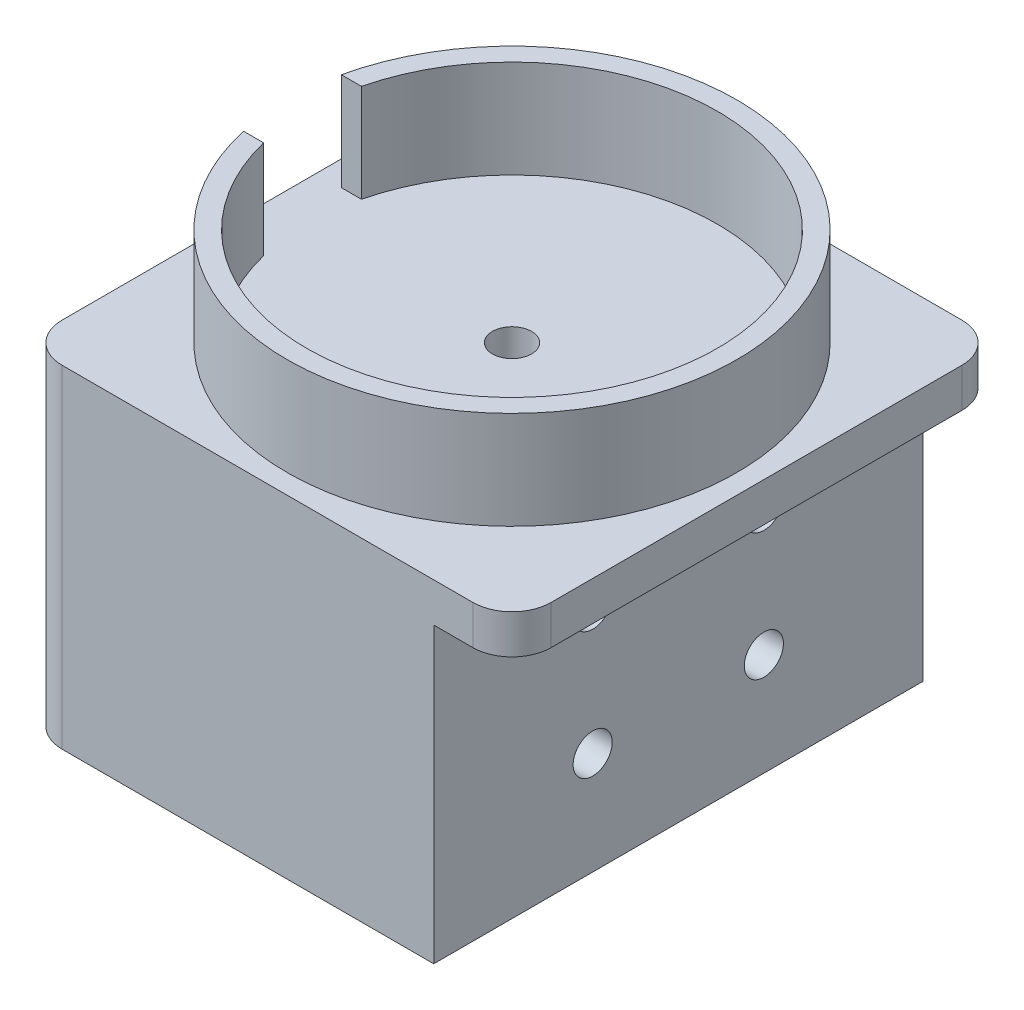
SolidWorks part; units mm, degrees
ref_plane "Front Plane" through (0, 0, 0) normal (0, 0, 1) x (1, 0, 0)
ref_plane "Top Plane" through (0, 0, 0) normal (0, 1, 0) x (1, 0, 0)
ref_plane "Right Plane" through (0, 0, 0) normal (1, 0, 0) x (0, 0, -1)
sketch "Sketch1" plane through (0, 0, 0) normal (0, 1, 0) x (1, 0, 0)
  line L0 (42, 50) -> (42, 0)
  line L1 (4, 0) -> (50, 0)
  line L2 (0, 4) -> (0, 46)
  line L3 (4, 50) -> (50, 50)
  line L4 (50, 0) -> (50, 50)
  arc A0 (4, 0) -> (0, 4) centre (4, 4) cw
  arc A1 (0, 46) -> (4, 50) centre (4, 46) cw
  point P7 (0, 0)
  point P10 (0, 50)
  dimension "D3" = 4
  dimension "D1" = 50
  dimension "D2" = 50
  dimension "D4" = 8
extrude "Boss-Extrude1" add sketch "Sketch1" along normal blind 30 contours A1 L2 A0 L1 L0 L3 region at (21.066, 0, -25)
sketch "Sketch3" plane through (0, 0, 0) normal (0, 0, 1) x (1, 0, 0)
  line L0 (42, 30) -> (42, 0) construction
  line L1 (34, 4) -> (0, 4)
  line L2 (34, 4) -> (34, 30)
  line L3 (34, 30) -> (0, 30)
  line L4 (0, 4) -> (0, 30)
  line L5 (0, 30) -> (0, 0) construction
  line L6 (4, 0) -> (42, 0) construction
  line L7 (4, 30) -> (42, 30) construction
  dimension "D1" = 8
  dimension "D2" = 0
  dimension "D3" = 4
  dimension "D4" = 0
extrude "Cut-Extrude1" cut sketch "Sketch3" against normal blind 35 from offset 7.5 offset against normal yes
sketch "Sketch6" plane through (0, 4, 0) normal (0, 1, 0) x (1, 0, 0)
  line L0 (0, 25) -> (34, 25)
  line L1 (0, 42.5) -> (0, 7.5) construction
  line L2 (34, 42.5) -> (34, 7.5) construction
  line L3 (25, 42.5) -> (25, 7.5)
  line L4 (0, 42.5) -> (34, 42.5) construction
  line L5 (0, 7.5) -> (34, 7.5) construction
  circle A0 centre (25, 25) radius 2
  circle A1 centre (15, 25) radius 2
  circle A2 centre (25, 15) radius 2
  circle A3 centre (25, 35) radius 2
  dimension "D2" = 4
  dimension "D3" = 10
  dimension "D1" = 25
  dimension "D4" = 10
  dimension "D5" = 10
hole_wizard "Ø4.0mm Dowel Hole2" positions "3DSketch2" profile "Sketch7" hole size "Ø4.0" standard "ANSI Metric" end condition through all
sketch3d "3DSketch2"
  point P0 (25, 4, -35)
  point P3 (25, 4, -25)
  point P6 (25, 4, -15)
  point P9 (15, 4, -25)
sketch "Sketch7" plane through (25, 4, -35) normal (1, 0, 0) x (0, 0, 1)
  line L0 (0, 0) -> (0, 4)
  line L1 (0, 4) -> (2, 4)
  line L2 (2, 4) -> (2, 0)
  line L5 (2, 0) -> (0, 0)
  line L11 (0, -6.35) -> (0, 107.95) construction
  dimension "Thru Hole Dia." = 4
  dimension "Thru Hole Depth" = 4
sketch "Sketch2" plane through (42, 0, 0) normal (1, 0, 0) x (0, 0, -1)
  line L0 (0, 1.5) -> (50, 1.5)
  line L1 (50, 30) -> (50, 0) construction
  line L2 (50, 1.5) -> (50, 7.5)
  line L3 (50, 7.5) -> (0, 7.5)
  line L4 (0, 30) -> (0, 0) construction
  line L5 (0, 7.5) -> (0, 1.5)
  line L6 (50, 0) -> (0, 0) construction
  line L8 (0, 13.5) -> (50, 13.5)
  line L9 (0, 13.5) -> (0, 19.5)
  line L10 (0, 19.5) -> (50, 19.5)
  line L11 (50, 13.5) -> (50, 19.5)
  line L12 (25, 30) -> (25, 0) construction
  line L13 (50, 30) -> (0, 30) construction
  circle A0 centre (16.25, 23.5) radius 2
  circle A1 centre (33.75, 23.5) radius 2
  circle A2 centre (33.75, 10.5) radius 2
  circle A3 centre (16.25, 10.5) radius 2
  point P22 (16.25, 23.5)
  point P27 (0, 0)
  point P28 (0, 0)
  dimension "D5" = 4
  dimension "D1" = 6
  dimension "D2" = 1.5
  dimension "D3" = 6
  dimension "D4" = 12
  dimension "D6" = 3
  dimension "D7" = 3
  dimension "D8" = 4
  dimension "D9" = 4
  dimension "D10" = 8.75
  dimension "D11" = 8.75
  dimension "D12" = 8.75
  dimension "D13" = 8.75
hole_wizard "Ø4.0mm Dowel Hole1" positions "3DSketch1" profile "Sketch4" hole size "Ø4.0" standard "ANSI Metric" end condition through all
sketch3d "3DSketch1"
  point P0 (42, 23.5, -16.25)
  point P3 (42, 23.5, -33.75)
  point P6 (42, 10.5, -33.75)
  point P9 (42, 10.5, -16.25)
sketch "Sketch4" plane through (42, 23.5, -16.25) normal (0, 1, 0) x (0, 0, -1)
  line L0 (0, 0) -> (0, 42)
  line L1 (0, 42) -> (2, 42)
  line L2 (2, 42) -> (2, 0)
  line L5 (2, 0) -> (0, 0)
  line L11 (0, -6.35) -> (0, 107.95) construction
  dimension "Thru Hole Dia." = 4
  dimension "Thru Hole Depth" = 42
sketch "Sketch5" plane through (0, 30, 0) normal (0, 1, 0) x (1, 0, 0)
  line L1 (4, 0) -> (46, 0)
  line L2 (0, 4) -> (0, 46)
  line L3 (4, 50) -> (46, 50)
  line L4 (50, 4) -> (50, 46)
  arc A0 (46, 50) -> (50, 46) centre (46, 46) cw
  arc A1 (46, 0) -> (50, 4) centre (46, 4) ccw
  arc A2 (4, 0) -> (0, 4) centre (4, 4) cw
  arc A3 (0, 46) -> (4, 50) centre (4, 46) cw
  point P7 (50, 50)
  point P12 (0, 0)
  point P15 (0, 50)
  dimension "D3" = 4
  dimension "D1" = 50
  dimension "D2" = 50
extrude "Boss-Extrude2" add sketch "Sketch5" along normal blind 4
sketch "Sketch8" plane through (0, 34, 0) normal (0, 1, 0) x (1, 0, 0)
  line L0 (46, 50) -> (4, 50) construction
  line L1 (0, 46) -> (0, 4) construction
  line L2 (2.5501, 30) -> (4.6039, 30)
  line L3 (4.6039, 20) -> (2.5501, 20)
  circle A0 centre (25, 25) radius 21
  circle A1 centre (25, 25) radius 23
  dimension "D1" = 42
  dimension "D4" = 2
  dimension "D2" = 25
  dimension "D3" = 25
  dimension "D5" = 10
  dimension "D6" = 5
extrude "Boss-Extrude3" add sketch "Sketch8" along normal blind 10 contours L3 A1 L2 A0 region at (27.4444, 34, -47.2193)
hole_wizard "Ø4.0mm Dowel Hole3" positions "3DSketch3" profile "Sketch9" hole size "Ø4.0" standard "ANSI Metric" end condition up to next
sketch3d "3DSketch3"
  line L0 (25, 44, -25) -> (25, 34, -25) construction
  point P0 (25, 44, -25)
sketch "Sketch9" plane through (25, 44, -25) normal (1, 0, 0) x (0, 0, 1)
  line L0 (0, 0) -> (0, 14)
  line L1 (0, 14) -> (2, 14)
  line L2 (2, 14) -> (2, 0)
  line L5 (2, 0) -> (0, 0)
  line L11 (0, -6.35) -> (0, 107.95) construction
  dimension "Thru Hole Dia." = 4
  dimension "Thru Hole Depth" = 14
